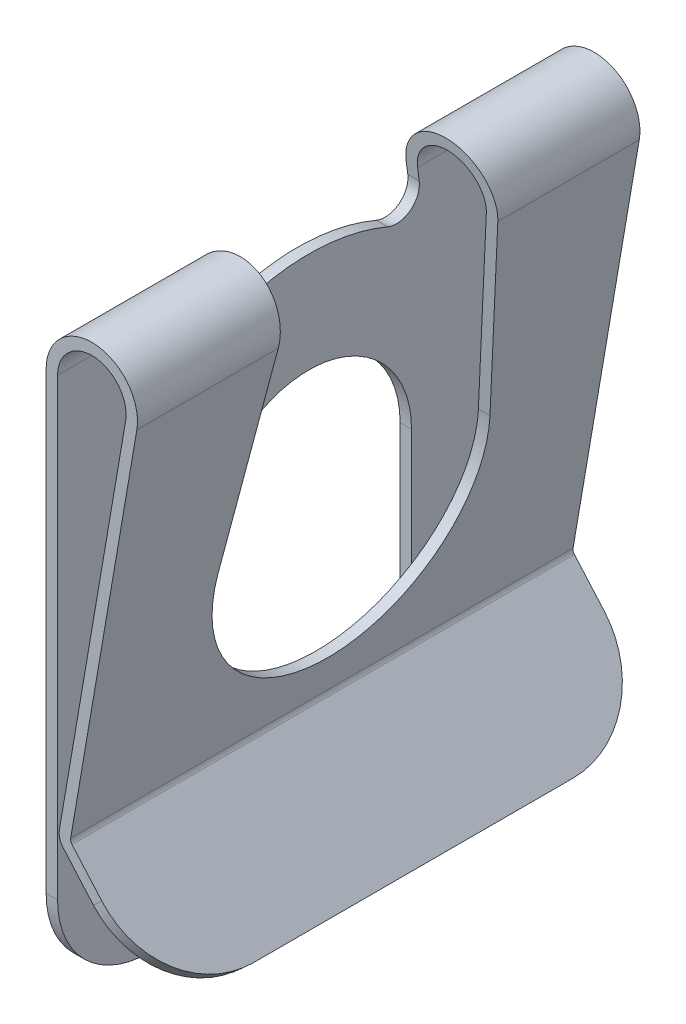
SolidWorks part; units mm, degrees
ref_plane "Front Plane" through (0, 0, 0) normal (0, 0, 1) x (1, 0, 0)
ref_plane "Top Plane" through (0, 0, 0) normal (0, 1, 0) x (1, 0, 0)
ref_plane "Right Plane" through (0, 0, 0) normal (1, 0, 0) x (0, 0, -1)
ref_plane "Plane1" through (0, 0, 0) normal (0, 0, 1) x (1, 0, 0)
sketch "Sketch1" plane through (0, 0, 0) normal (0, 0, 1) x (1, 0, 0)
  line L0 (0, 9.8) -> (0, -14.1)
  line L1 (0, -14.1) -> (0.5, -14.1)
  line L2 (0.5, -14.1) -> (0.5, 9.8)
  line L3 (3.4785, 9.547) -> (0.5805, -7.3879)
  line L4 (0.7552, -8.0082) -> (4.7004, -12.5186)
  line L5 (4.7004, -12.5186) -> (5.0768, -12.1894)
  line L6 (5.0768, -12.1894) -> (1.1315, -7.679)
  line L7 (1.0733, -7.4722) -> (3.9713, 9.4626)
  arc A0 (0.5, 9.8) -> (3.4785, 9.547) centre (2, 9.8) cw
  arc A1 (0.5805, -7.3879) -> (0.7552, -8.0082) centre (1.3197, -7.5144) ccw
  arc A2 (1.1315, -7.679) -> (1.0733, -7.4722) centre (1.3197, -7.5144) cw
  arc A3 (3.9713, 9.4626) -> (0, 9.8) centre (2, 9.8) ccw
extrude "Boss-Extrude1" add sketch "Sketch1" against normal blind 11 and the other way blind 11
ref_plane "Plane2" through (0, 0, 0) normal (1, 0, 0) x (0, 0, -1)
sketch "Sketch2" plane through (0, 0, 0) normal (1, 0, 0) x (0, 0, -1)
  line L0 (-4.5, 0) -> (-4.5, -14.1)
  line L1 (-4.5, -14.1) -> (4.5, -14.1)
  line L2 (4.5, -14.1) -> (4.5, 0)
  arc A0 (4.5, 0) -> (-4.5, 0) centre (0, 0) ccw
extrude "Cut-Extrude1" cut sketch "Sketch2" along normal blind 0.5
ref_plane "Plane3" through (0.5, 0, 0) normal (1, 0, 0) x (0, 0, -1)
sketch "Sketch3" plane through (0.5, 0, 0) normal (1, 0, 0) x (0, 0, -1)
  line L0 (5.9488, 0.7822) -> (4.5, 11.8)
  line L1 (4.5, 11.8) -> (-4.5, 11.8)
  line L2 (-4.5, 11.8) -> (-5.9488, 0.7822)
  arc A0 (-5.9488, 0.7822) -> (5.9488, 0.7822) centre (0, 0) ccw
extrude "Cut-Extrude2" cut sketch "Sketch3" along normal blind 5
ref_plane "Plane4" through (0.5, 0, 0) normal (1, 0, 0) x (0, 0, -1)
sketch "Sketch4" plane through (0.5, 0, 0) normal (1, 0, 0) x (0, 0, -1)
  line L0 (4.8348, 9.2539) -> (4.5, 11.8)
  line L1 (4.5, 11.8) -> (-4.5, 11.8)
  line L2 (-4.5, 11.8) -> (-4.8348, 9.2539)
  arc A0 (-4.8348, 9.2539) -> (-3.4551, 8.202) centre (-3.8433, 9.1235) ccw
  arc A1 (-3.4551, 8.202) -> (3.4551, 8.202) centre (0, 0) cw
  arc A2 (3.4551, 8.202) -> (4.8348, 9.2539) centre (3.8433, 9.1235) ccw
extrude "Cut-Extrude3" cut sketch "Sketch4" against normal blind 5
ref_plane "Plane5" through (0, 0, 0) normal (1, 0, 0) x (0, 0, -1)
sketch "Sketch5" plane through (0, 0, 0) normal (1, 0, 0) x (0, 0, -1)
  line L0 (-11, -14.1) -> (-7, -14.1)
  line L1 (-11, -10.1) -> (-11, -14.1)
  arc A0 (-7, -14.1) -> (-11, -10.1) centre (-7, -10.1) cw
extrude "Cut-Extrude4" cut sketch "Sketch5" along normal blind 0.5
ref_plane "Plane6" through (0, 0, 0) normal (1, 0, 0) x (0, 0, -1)
sketch "Sketch6" plane through (0, 0, 0) normal (1, 0, 0) x (0, 0, -1)
  line L0 (7, -14.1) -> (11, -14.1)
  line L1 (11, -14.1) -> (11, -10.1)
  arc A0 (11, -10.1) -> (7, -14.1) centre (7, -10.1) cw
extrude "Cut-Extrude5" cut sketch "Sketch6" along normal blind 0.5
ref_plane "Plane7" through (0, 0, 0) normal (1, 0, 0) x (0, 0, -1)
sketch "Sketch7" plane through (0, 0, 0) normal (1, 0, 0) x (0, 0, -1)
  line L0 (4.5, -14.1) -> (5.5, -14.1)
  line L1 (4.5, -13.1) -> (4.5, -14.1)
  arc A0 (5.5, -14.1) -> (4.5, -13.1) centre (5.5, -13.1) cw
extrude "Cut-Extrude6" cut sketch "Sketch7" along normal blind 0.5
ref_plane "Plane8" through (0, 0, 0) normal (1, 0, 0) x (0, 0, -1)
sketch "Sketch8" plane through (0, 0, 0) normal (1, 0, 0) x (0, 0, -1)
  line L0 (-5.5, -14.1) -> (-4.5, -14.1)
  line L1 (-4.5, -14.1) -> (-4.5, -13.1)
  arc A0 (-4.5, -13.1) -> (-5.5, -14.1) centre (-5.5, -13.1) cw
extrude "Cut-Extrude7" cut sketch "Sketch8" along normal blind 0.5
ref_plane "Plane9" through (-3.1643, -2.7678, 0) normal (0.7527, 0.6584, 0) x (0, 0, -1)
sketch "Sketch9" plane through (-3.1643, -2.7678, 0) normal (0.7527, 0.6584, 0) x (0, 0, -1)
  line L0 (-11, -8.5169) -> (-15, -8.5169)
  line L1 (-15, -8.5169) -> (-15, -16.5169)
  line L2 (-15, -16.5169) -> (15, -16.5169)
  line L3 (15, -16.5169) -> (15, -8.5169)
  line L4 (15, -8.5169) -> (11, -8.5169)
  line L5 (7, -12.5169) -> (-7, -12.5169)
  arc A0 (11, -8.5169) -> (7, -12.5169) centre (7, -8.5169) cw
  arc A1 (-7, -12.5169) -> (-11, -8.5169) centre (-7, -8.5169) cw
extrude "Cut-Extrude8" cut sketch "Sketch9" against normal blind 1 and the other way blind 1
